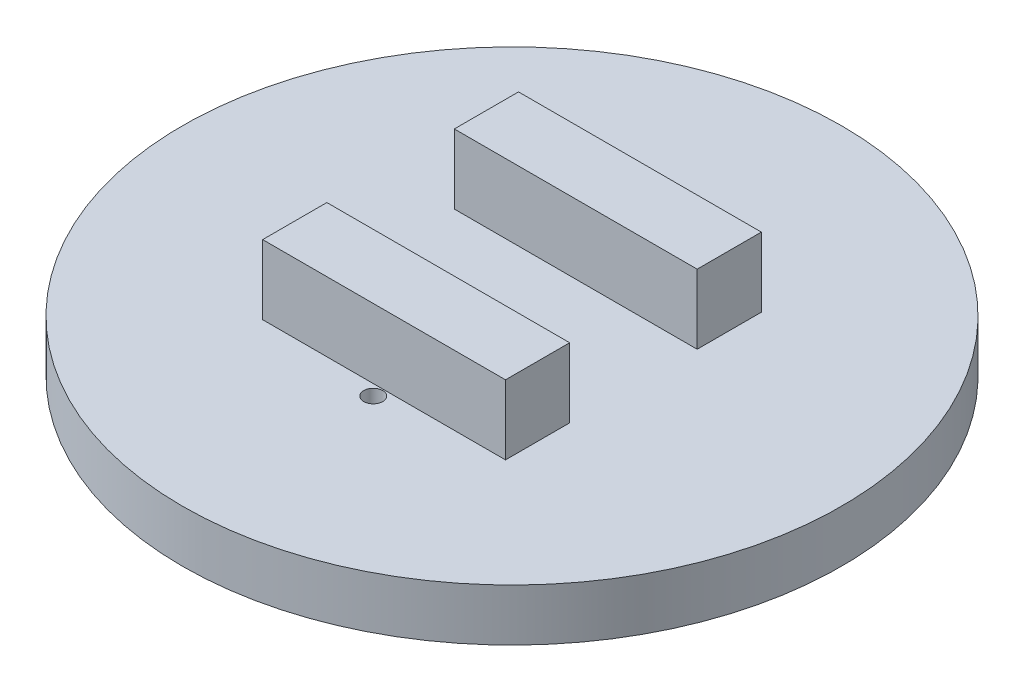
SolidWorks part; units mm, degrees
ref_plane "Front Plane" through (0, 0, 0) normal (0, 0, 1) x (1, 0, 0)
ref_plane "Top Plane" through (0, 0, 0) normal (0, 1, 0) x (1, 0, 0)
ref_plane "Right Plane" through (0, 0, 0) normal (1, 0, 0) x (0, 0, -1)
sketch "Sketch1" plane through (0, 0, 0) normal (0, 1, 0) x (1, 0, 0)
  circle A0 centre (0, 0) radius 95
  dimension "D1" = 190
extrude "Boss-Extrude1" add sketch "Sketch1" along normal blind 15
sketch "Sketch2" plane through (0, 0, 0) normal (0, 0, 1) x (1, 0, 0)
  line L0 (95, 15) -> (-95, 15) construction
  line L1 (-94.9614, 15) -> (-88.9614, 15)
  line L2 (-94.9614, 15) -> (-94.9614, 140)
  line L3 (-94.9614, 140) -> (-88.9614, 140)
  line L4 (-88.9614, 15) -> (-88.9614, 140)
  line L6 (0, 0) -> (0, 135) construction
  line L7 (-78.9614, 15) -> (-72.9614, 15)
  line L8 (-78.9614, 15) -> (-78.9614, 135)
  line L9 (-78.9614, 135) -> (-72.9614, 135)
  line L10 (-72.9614, 15) -> (-72.9614, 135)
  dimension "D1" = 125
  dimension "D2" = 6
  dimension "D3" = 10
  dimension "D4" = 120
  dimension "D5" = 6
sketch "Sketch4" plane through (0, 15, 0) normal (0, 1, 0) x (1, 0, 0)
  line L0 (0, 0) -> (0, -40) construction
  line L1 (0, 0) -> (0, 40) construction
  circle A0 centre (0, 40) radius 2.75
  circle A1 centre (0, -40) radius 2.75
  dimension "D3" = 5.5
  dimension "D4" = 5.5
  dimension "D1" = 40
  dimension "D2" = 40
extrude "Cut-Extrude1" cut sketch "Sketch4" against normal blind 5
sketch "Sketch8" plane through (0, 15, 0) normal (0, 1, 0) x (1, 0, 0)
  line L0 (0, 0) -> (0, 18) construction
  line L1 (0, 0) -> (0, -18) construction
  line L2 (0, 40) -> (0, 37.25) construction
  line L3 (0, 18) -> (0, 27.625) construction
  line L4 (0, -18) -> (0, -27.625) construction
  line L5 (-35, 18.375) -> (35, 18.375)
  line L6 (-35, 18.375) -> (-35, 36.875)
  line L7 (-35, 36.875) -> (35, 36.875)
  line L8 (35, 18.375) -> (35, 36.875)
  line L9 (-35, 18.375) -> (35, 36.875) construction
  line L10 (-35, 36.875) -> (35, 18.375) construction
  line L12 (-35, -36.875) -> (35, -36.875)
  line L13 (-35, -36.875) -> (-35, -18.375)
  line L14 (-35, -18.375) -> (35, -18.375)
  line L15 (35, -36.875) -> (35, -18.375)
  line L16 (-35, -36.875) -> (35, -18.375) construction
  line L17 (-35, -18.375) -> (35, -36.875) construction
  circle A0 centre (0, 40) radius 2.75 construction
  dimension "D1" = 18
  dimension "D2" = 18
  dimension "D3" = 9.625
  dimension "D4" = 18.5
  dimension "D5" = 70
  dimension "D6" = 9.625
  dimension "D7" = 18.5
  dimension "D8" = 70
extrude "Boss-Extrude3" add sketch "Sketch8" along normal blind 20
